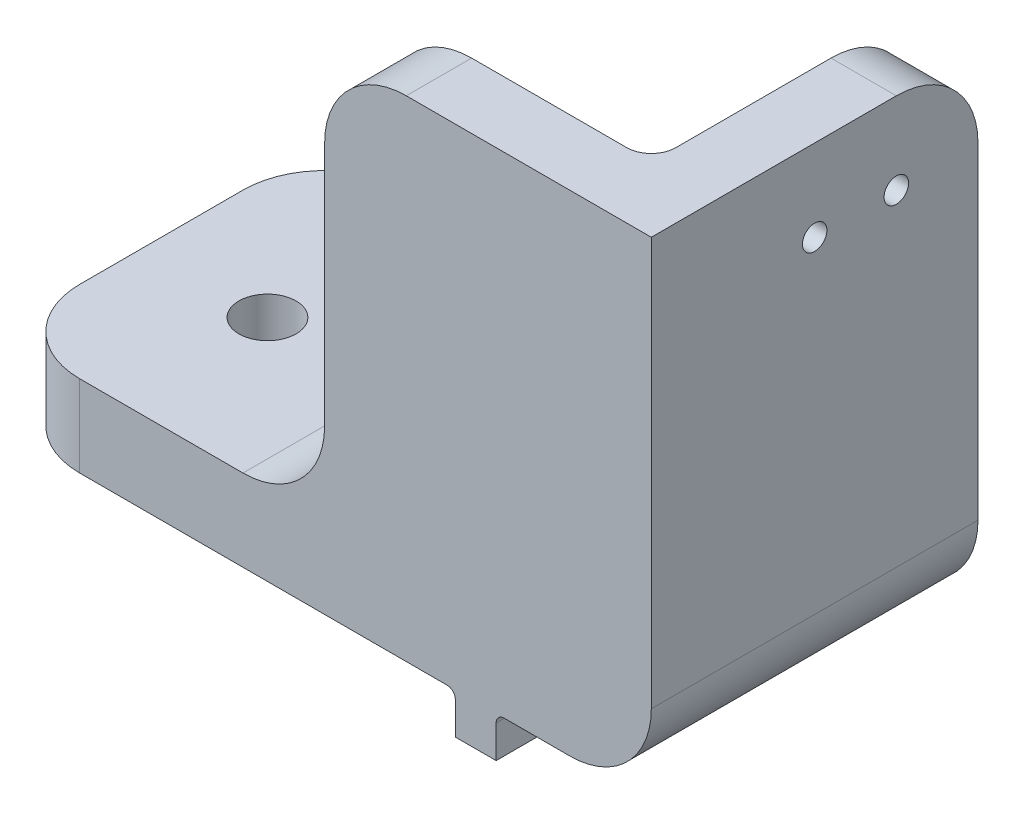
SolidWorks part; units mm, degrees
ref_plane "Front Plane" through (0, 0, 0) normal (0, 0, 1) x (1, 0, 0)
ref_plane "Top Plane" through (0, 0, 0) normal (0, 1, 0) x (1, 0, 0)
ref_plane "Right Plane" through (0, 0, 0) normal (1, 0, 0) x (0, 0, -1)
sketch "Sketch1" plane through (0, 0, 0) normal (0, 1, 0) x (1, 0, 0)
  line L0 (80, 20) -> (0, 20) construction
  line L1 (0, 0) -> (80, 0)
  line L2 (0, 0) -> (0, 40)
  line L3 (0, 40) -> (80, 40)
  line L4 (80, 0) -> (80, 40)
  line L5 (0, 30) -> (80, 30) construction
  line L7 (0, 18) -> (80, 18) construction
  circle A2 centre (65, 30) radius 1.6
  circle A3 centre (50, 30) radius 1.6
  circle A6 centre (50, 18) radius 1.6
  circle A7 centre (65, 18) radius 1.6
  point P19 (0, 0)
  dimension "D3" = 10
  dimension "D4" = 18
  dimension "D5" = 15
  dimension "D6" = 15
  dimension "D7" = 3.2
  dimension "D1" = 40
  dimension "D2" = 80
extrude "Boss-Extrude1" add sketch "Sketch1" along normal blind 10
sketch "Sketch2" plane through (0, 10, 0) normal (0, 1, 0) x (1, 0, 0)
  line L0 (80, 40) -> (0, 40) construction
  line L1 (0, 0) -> (8, 0)
  line L2 (0, 0) -> (0, 40)
  line L3 (0, 40) -> (8, 40)
  line L4 (8, 0) -> (8, 40)
  line L6 (0, 0) -> (40, 0)
  line L7 (0, 0) -> (0, 8)
  line L8 (0, 8) -> (40, 8)
  line L9 (40, 0) -> (40, 8)
  line M4 (0, 40) -> (0, 0)
  line M5 (0, 0) -> (80, 0)
  line M7 (80, 40) -> (0, 40)
  dimension "D1" = 8
  dimension "D2" = 8
  dimension "D3" = 40
extrude "Boss-Extrude2" add sketch "Sketch2" along normal blind 50 contours L8 L4 M4 M7 | L8 L2 L4 M5 | L9 L8 L4 M5 region at (4, 10, -4) region at (24, 10, -4) region at (4, 10, -24)
fillet "Fillet1" radius 10 5 edges at (4, 60, -40) (40, 60, -4) (80, 5, -40) (80, 5, 0) (40, 10, -4)
fillet "Fillet2" radius 3 2 edges at (8, 10, -24) (29, 10, -8)
sketch "Sketch3" plane through (0, 10, 0) normal (0, 1, 0) x (1, 0, 0)
  circle A0 centre (50, 30) radius 3.5
  circle A1 centre (50, 18) radius 3.5
  circle A2 centre (65, 18) radius 3.5
  circle A3 centre (65, 30) radius 3.5
  dimension "D1" = 7
extrude "Cut-Extrude1" cut sketch "Sketch3" against normal blind 5
fillet "Fillet3" radius 10 1 edges at (0, 0, -20)
sketch "Sketch4" plane through (0, 0, 0) normal (0, -1, 0) x (1, 0, 0)
  line L0 (10, 0) -> (70, 0) construction
  line L1 (19, 0) -> (24, 0)
  line L2 (19, 0) -> (19, -40)
  line L3 (19, -40) -> (24, -40)
  line L4 (24, 0) -> (24, -40)
  line L5 (70, -40) -> (10, -40) construction
  line L7 (0, -40) -> (0, 0) construction
  dimension "D1" = 24
  dimension "D2" = 5
extrude "Boss-Extrude3" add sketch "Sketch4" along normal blind 5
fillet "Fillet4" radius 1 2 edges at (24, 0, -20) (19, 0, -20)
mirror "Mirror1" about plane through (80, 10, 0) normal (-1, 0, 0) of bodies 104
sketch "Sketch5" plane through (0, 0, 0) normal (-1, 0, 0) x (0, 0, 1)
  line L1 (-40, -5) -> (0, -5)
  line L2 (-40, -5) -> (-40, 60)
  line L3 (-40, 60) -> (0, 60)
  line L4 (0, -5) -> (0, 60)
extrude "Cut-Extrude2" cut sketch "Sketch5" against normal blind 80
fillet "Fillet5" radius 3 2 edges at (151.1213, 10.8787, -8.8787) (152, 36.5, -8)
sketch "Sketch6" plane through (160, 0, 0) normal (1, 0, 0) x (0, 0, -1)
  line L0 (30, 60) -> (30, 50) construction
  line L1 (30, 50) -> (40, 50) construction
  line L2 (20, 50) -> (30, 50) construction
  circle A0 centre (30, 50) radius 1.5
  circle A1 centre (20, 50) radius 1.5
  dimension "D1" = 3
  dimension "D2" = 10
extrude "Cut-Extrude3" cut sketch "Sketch6" against normal blind 80
